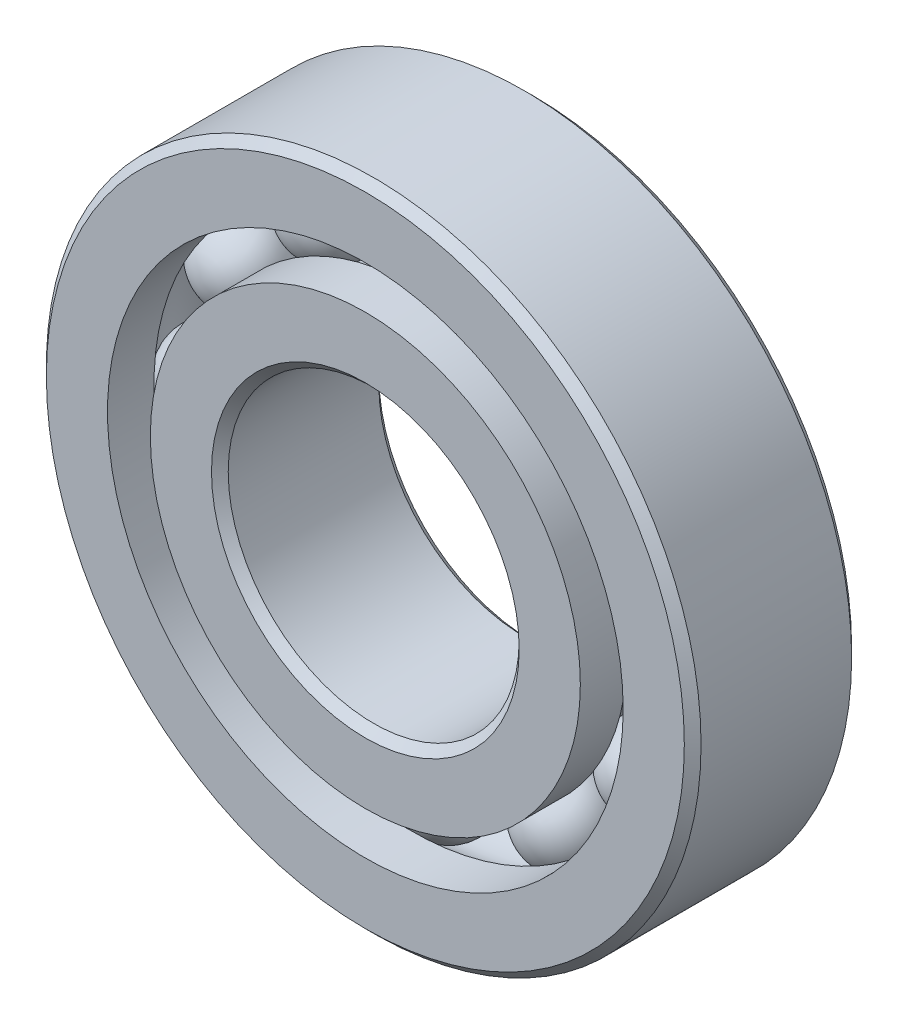
SolidWorks part; units mm, degrees
ref_plane "Front Plane" through (0, 0, 0) normal (0, 0, 1) x (1, 0, 0)
ref_plane "Top Plane" through (0, 0, 0) normal (0, 1, 0) x (1, 0, 0)
ref_plane "Right Plane" through (0, 0, 0) normal (1, 0, 0) x (0, 0, -1)
sketch "Sketch1" plane through (0, 0, 0) normal (1, 0, 0) x (0, 0, -1)
  line L0 (-11.5, 0) -> (11.5, 0) construction
  line L1 (0, 45) -> (0, -45) construction
  line L2 (10.35, 45) -> (-10.35, 45)
  line L3 (-10.35, 45) -> (-11.5, 43.85)
  line L4 (-11.5, 43.85) -> (-11.5, 35.4451)
  line L5 (-11.5, 35.4451) -> (-5.1111, 35.4451)
  line L6 (11.5, 35.4451) -> (5.1111, 35.4451)
  line L7 (11.5, 43.85) -> (11.5, 35.4451)
  line L8 (10.35, 45) -> (11.5, 43.85)
  line L9 (0, 45) -> (0, 32.5) construction
  line L10 (0, 32.5) -> (0, 20) construction
  arc A0 (-5.1111, 35.4451) -> (5.1111, 35.4451) centre (0, 32.5) cw
  point P14 (0, 20)
  dimension "D3" = 10.2222
  dimension "D1" = 45
  dimension "Width" = 23
  dimension "OD" = 90
  dimension "D2" = 1.15
  dimension "Shaft Dia" = 40
  dimension "D4" = 2.9451
revolve "Revolve1" add sketch "Sketch1" angle 360 about L0
sketch "Sketch3" plane through (0, 0, 0) normal (1, 0, 0) x (0, 0, -1)
  line L0 (-11.5, 29.5549) -> (-5.1111, 29.5549)
  line L1 (0, 45) -> (0, -45) construction
  line L2 (-11.5, 43.85) -> (-11.5, 35.4451) construction
  line L3 (-11.5, 29.5549) -> (-11.5, 21.15)
  line L4 (-10.35, 45) -> (-11.5, 43.85) construction
  line L5 (-11.5, 21.15) -> (-10.35, 20)
  line L6 (-10.35, 20) -> (10.35, 20)
  line L7 (10.35, 45) -> (10.35, -45) construction
  line L8 (10.35, 20) -> (11.5, 21.15)
  line L9 (11.5, -43.85) -> (11.5, 43.85) construction
  line L10 (11.5, 21.15) -> (11.5, 29.5549)
  line L11 (11.5, 29.5549) -> (5.1111, 29.5549)
  line L13 (10.35, 45) -> (11.5, 43.85) construction
  arc A0 (5.1111, 35.4451) -> (-5.1111, 35.4451) centre (0, 32.5) ccw construction
  arc A1 (5.1111, 29.5549) -> (-5.1111, 29.5549) centre (0, 32.5) cw
revolve "Revolve3" add sketch "Sketch3" angle 360 about L0
sketch "Sketch4" plane through (0, 0, 0) normal (1, 0, 0) x (0, 0, -1)
  line L0 (-5.8989, 32.5) -> (5.8989, 32.5)
  arc A2 (-5.8989, 32.5) -> (5.8989, 32.5) centre (0, 32.5) cw
  arc A3 (5.1111, 35.4451) -> (-5.1111, 35.4451) centre (0, 32.5) ccw construction
revolve "Revolve4" add sketch "Sketch4" angle 360 about L0
ref_axis "Axis1" through (0, 0, -11.5) along (0, 0, 1)
pattern_circular "CirPattern1" count 12 every 30 about axis through (0, 0, -11.5) along (0, 0, 1) of bodies 104
sketch "Sketch5" plane through (0, 0, 0) normal (1, 0, 0) x (0, 0, -1)
  line L0 (-11.5, 35.4451) -> (-5.1111, 35.4451) construction
  line L1 (-10.925, 35.4451) -> (-5.8989, 35.4451)
  line L2 (-10.925, 35.4451) -> (-10.925, 29.5549)
  line L3 (-10.925, 29.5549) -> (-5.8989, 29.5549)
  line L4 (-5.8989, 35.4451) -> (-5.8989, 29.5549)
  line L5 (-11.5, 29.5549) -> (-5.1111, 29.5549) construction
  line L6 (11.5, 35.4451) -> (5.1111, 35.4451) construction
  line L7 (10.925, 35.4451) -> (5.8989, 35.4451)
  line L8 (10.925, 35.4451) -> (10.925, 29.5549)
  line L9 (10.925, 29.5549) -> (5.8989, 29.5549)
  line L10 (5.8989, 35.4451) -> (5.8989, 29.5549)
  line L11 (11.5, 29.5549) -> (5.1111, 29.5549) construction
  line L12 (-10.35, 45) -> (-11.5, 43.85) construction
  point P18 (-10.925, 44.425)
equation "\"D2@Sketch1\" = \"Width@Sketch1\"*.05"
equation "\"D3@Sketch1\" = \"Width@Sketch1\"/2.25"
equation "\"D4@Sketch1\" = (((\"OD@Sketch1\"-\"Width@Sketch1\")/2)/3.25)/3.5"
equation "\"D2@CirPattern1\" = 360/\"Balls@CirPattern1\""
